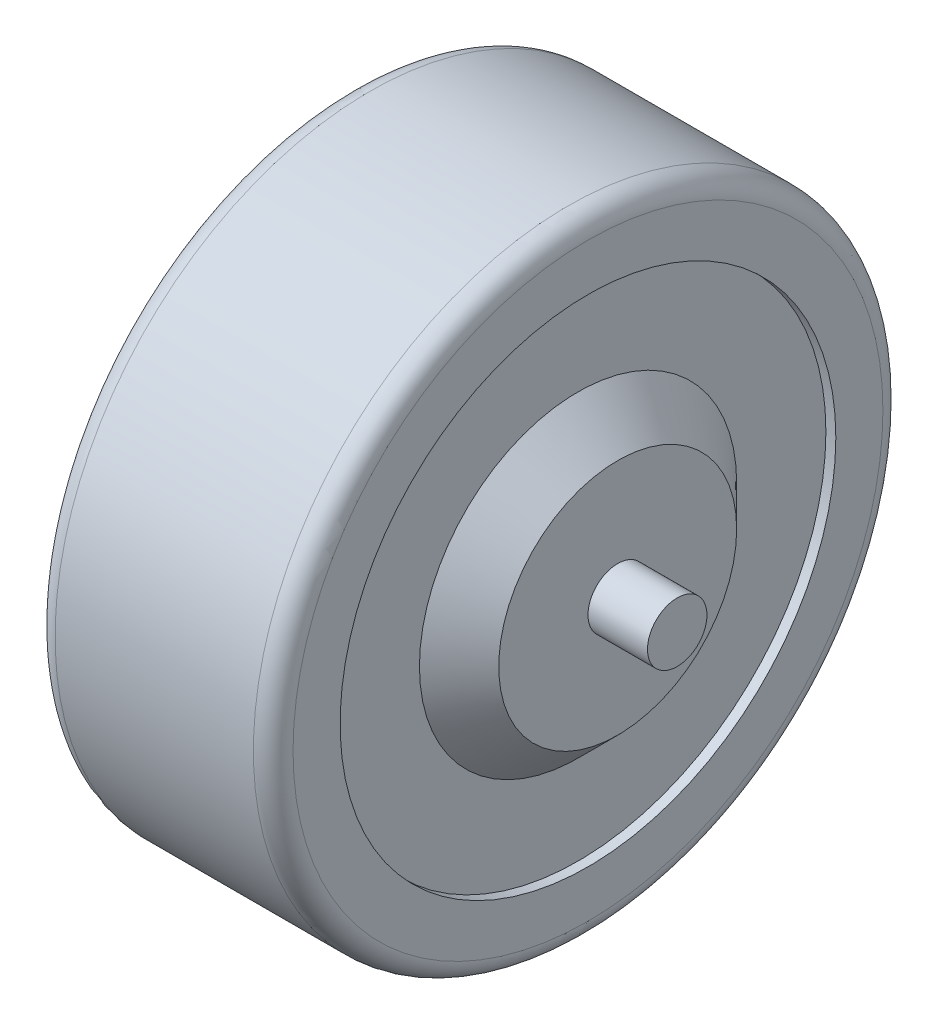
SolidWorks part; units mm, degrees
ref_plane "Front Plane" through (0, 0, 0) normal (0, 0, 1) x (1, 0, 0)
ref_plane "Top Plane" through (0, 0, 0) normal (0, 1, 0) x (1, 0, 0)
ref_plane "Right Plane" through (0, 0, 0) normal (1, 0, 0) x (0, 0, -1)
sketch "Sketch1" plane through (0, 0, 0) normal (1, 0, 0) x (0, 0, -1)
  circle A0 centre (0, 0) radius 31.75
  dimension "D1" = 63.5
extrude "Boss-Extrude1" add sketch "Sketch1" along normal blind 12 and the other way blind 12
sketch "Sketch2" plane through (12, 0, 0) normal (1, 0, 0) x (0, 0, -1)
  circle A0 centre (0, 0) radius 25
  circle A1 centre (0, 0) radius 16
  dimension "D1" = 32
  dimension "D2" = 50
extrude "Cut-Extrude1" cut sketch "Sketch2" against normal blind 1
sketch "Sketch3" plane through (12, 0, 0) normal (1, 0, 0) x (0, 0, -1)
  circle A1 centre (0, 0) radius 16
  circle A2 centre (0, 0) radius 16
  dimension "D1" = 0
extrude "Boss-Extrude2" add sketch "Sketch3" along normal blind 3
mirror "Mirror1" about plane through (0, 0, 0) normal (1, 0, 0) of "Boss-Extrude2", "Cut-Extrude1"
chamfer "Chamfer2" distance 4 angle 45 2 edges at (-15, 0, -16) (15, 0, -16)
fillet "Fillet1" radius 2 2 edges at (12, 0, -31.75) (-12, 0, -31.75)
sketch "Sketch4" plane through (15, 0, 0) normal (1, 0, 0) x (0, 0, -1)
  circle A0 centre (0, 0) radius 3
  dimension "D1" = 6
extrude "Boss-Extrude3" add sketch "Sketch4" along normal blind 6
mirror "Mirror2" about plane through (0, 0, 0) normal (1, 0, 0) of "Boss-Extrude3"
scale "Scale1" scale about centroid uniform scaling yes scale factor 0.7761
